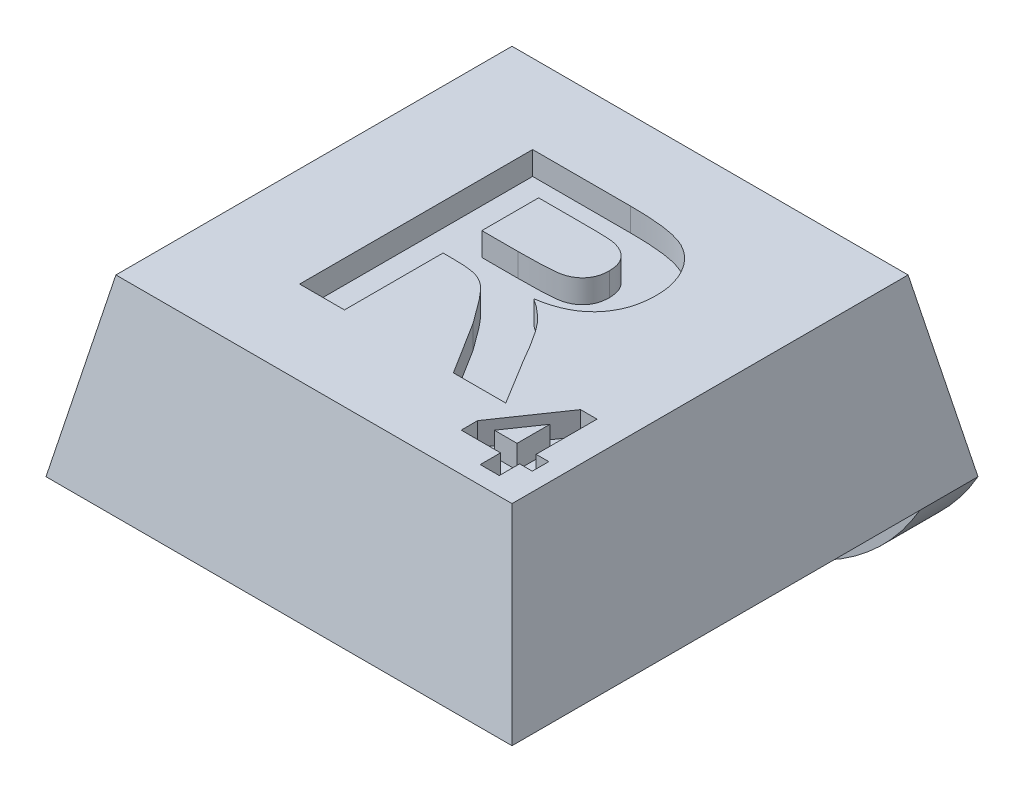
SolidWorks part; units mm, degrees
ref_plane "Front Plane" through (0, 0, 0) normal (0, 0, 1) x (1, 0, 0)
ref_plane "Top Plane" through (0, 0, 0) normal (0, 1, 0) x (1, 0, 0)
ref_plane "Right Plane" through (0, 0, 0) normal (1, 0, 0) x (0, 0, -1)
sketch "Sketch1" plane through (0, 0, 0) normal (0, 1, 0) x (1, 0, 0)
  line L1 (0, 0) -> (8, 0)
  line L2 (0, 0) -> (0, 8)
  line L3 (0, 8) -> (8, 8)
  line L4 (8, 0) -> (8, 8)
  dimension "D1" = 8
  dimension "D2" = 8
extrude "Boss-Extrude1" add sketch "Sketch1" along normal blind 3
sketch "Sketch2" plane through (0, 0, 0) normal (0, 0, 1) x (1, 0, 0)
  line L0 (0, 0) -> (0.6, 3)
  line L1 (0, 3) -> (8, 3) construction
  line L2 (0.6, 3) -> (0, 3)
  line L3 (0, 3) -> (0, 0)
  line L4 (8, 0) -> (7.4, 3)
  line L5 (7.4, 3) -> (8, 3)
  line L6 (8, 3) -> (8, 0)
  dimension "D1" = 0.6
  dimension "D2" = 0.6
extrude "Cut-Extrude1" cut sketch "Sketch2" against normal through all both and the other way through all
sketch "Sketch3" plane through (0, 0, 0) normal (1, 0, 0) x (0, 0, -1)
  line L0 (0, 0) -> (0.6, 3)
  line L1 (8, 3) -> (0, 3) construction
  line L2 (0.6, 3) -> (0, 3)
  line L3 (0, 3) -> (0, 0)
  line L4 (8, 3) -> (7.4, 3)
  line L5 (7.4, 3) -> (8, 0)
  line L6 (8, 3) -> (8, 0)
  dimension "D1" = 0.6
  dimension "D2" = 0.6
extrude "Cut-Extrude2" cut sketch "Sketch3" along normal blind 11
sketch "Sketch4" plane through (0, 0, 0) normal (0, -1, 0) x (1, 0, 0)
  line L0 (8, 0) -> (8, -8) construction
  line L3 (0, 0) -> (8, 0) construction
  circle A0 centre (4, -3.75) radius 1.8
  dimension "D1" = 3.6
  dimension "D2" = 4
  dimension "D3" = 3.75
extrude "Cut-Extrude3" cut sketch "Sketch4" against normal blind 0.8
sketch "Sketch5" plane through (0, 0, 0) normal (0, -1, 0) x (1, 0, 0)
  line L0 (8, 0) -> (8, -8) construction
  line L1 (0, -8) -> (8, -8)
  line L2 (0, -8) -> (0, -7)
  line L3 (0, -7) -> (8, -7)
  line L4 (8, -8) -> (8, -7)
  dimension "D1" = 1
extrude "Boss-Extrude2" add sketch "Sketch5" along normal blind 2
fillet "Fillet1" radius 4 2 edges at (8, -2, -7.5) (0, -2, -7.5)
sketch "Sketch6" plane through (0, 3, 0) normal (0, 1, 0) x (1, 0, 0)
  text T0 "R" font "Arial" height 4
extrude "Cut-Extrude4" cut sketch "Sketch6" against normal blind 0.4
sketch "Sketch7" plane through (0, 3, 0) normal (0, 1, 0) x (1, 0, 0)
  text T0 "4" font "Arial" height 1.7
extrude "Cut-Extrude5" cut sketch "Sketch7" against normal blind 0.4
